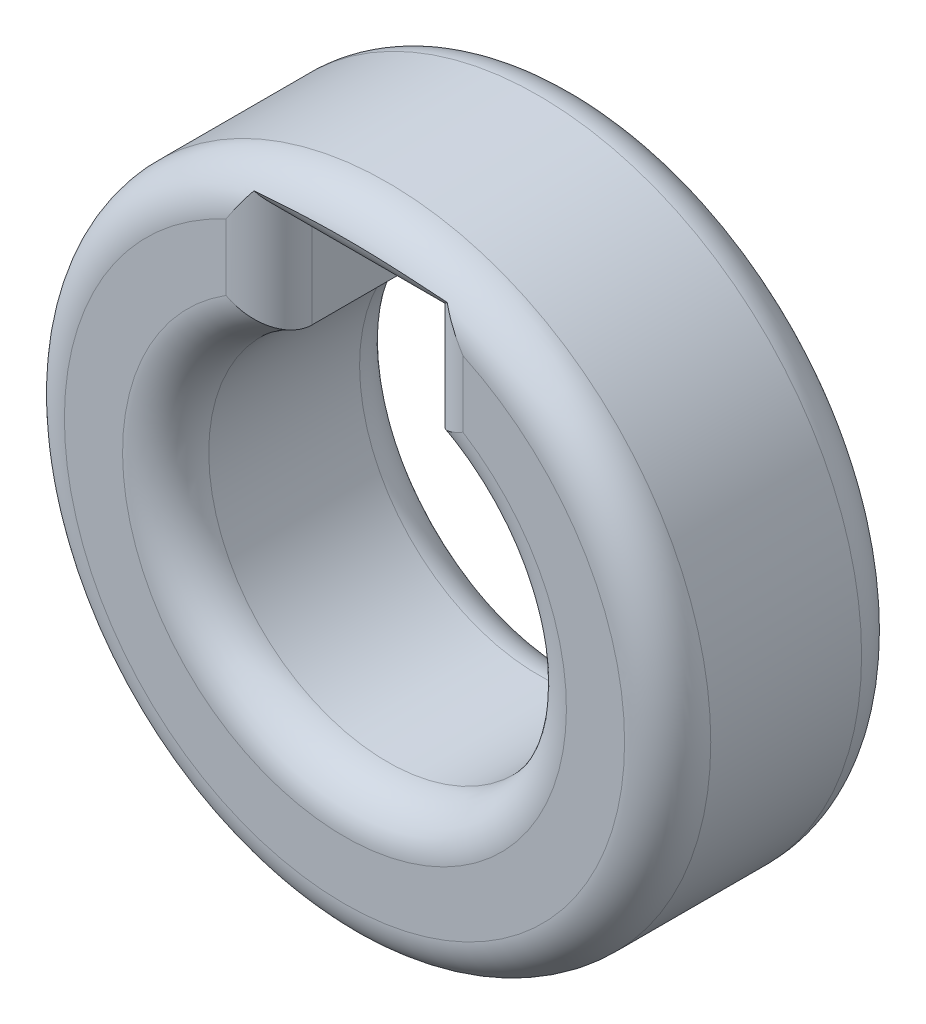
SolidWorks part; units mm, degrees
ref_plane "Ebene vorne" through (0, 0, 0) normal (0, 0, 1) x (1, 0, 0)
ref_plane "Ebene oben" through (0, 0, 0) normal (0, 1, 0) x (1, 0, 0)
ref_plane "Ebene rechts" through (0, 0, 0) normal (1, 0, 0) x (0, 0, -1)
sketch "Skizze1" plane through (0, 0, 0) normal (0, 0, 1) x (1, 0, 0)
  line L1 (-1.75, 2.15) -> (1.75, 2.15)
  line L2 (-1.75, 2.15) -> (-1.75, 6.15)
  line L3 (-1.75, 6.15) -> (1.75, 6.15)
  line L4 (1.75, 2.15) -> (1.75, 6.15)
  line L5 (-1.75, 2.15) -> (1.75, 6.15) construction
  line L6 (-1.75, 6.15) -> (1.75, 2.15) construction
  circle A0 centre (0, 0) radius 4.15
  circle A1 centre (0, 0) radius 7.5
  point P4 (0, 4.15)
  dimension "D1" = 8.3
  dimension "D2" = 15
  dimension "D3" = 3.5
  dimension "D4" = 4
extrude "Aufsatz-Linear austragen1" add sketch "Skizze1" along normal blind 5.5 contours A1 A0 L2 L3 L4 region at (-7.2879, 0, 0)
fillet "Verrundung1" radius 1 10 edges at (7.5, 0, 0) (-1.75, 4.9565, 0) (0, 6.15, 0) (1.75, 4.9565, 0) (0, -4.15, 0) (7.5, 0, 5.5) (1.75, 4.9565, 5.5) (0, 6.15, 5.5) (-1.75, 4.9565, 5.5) (0, -4.15, 5.5)
